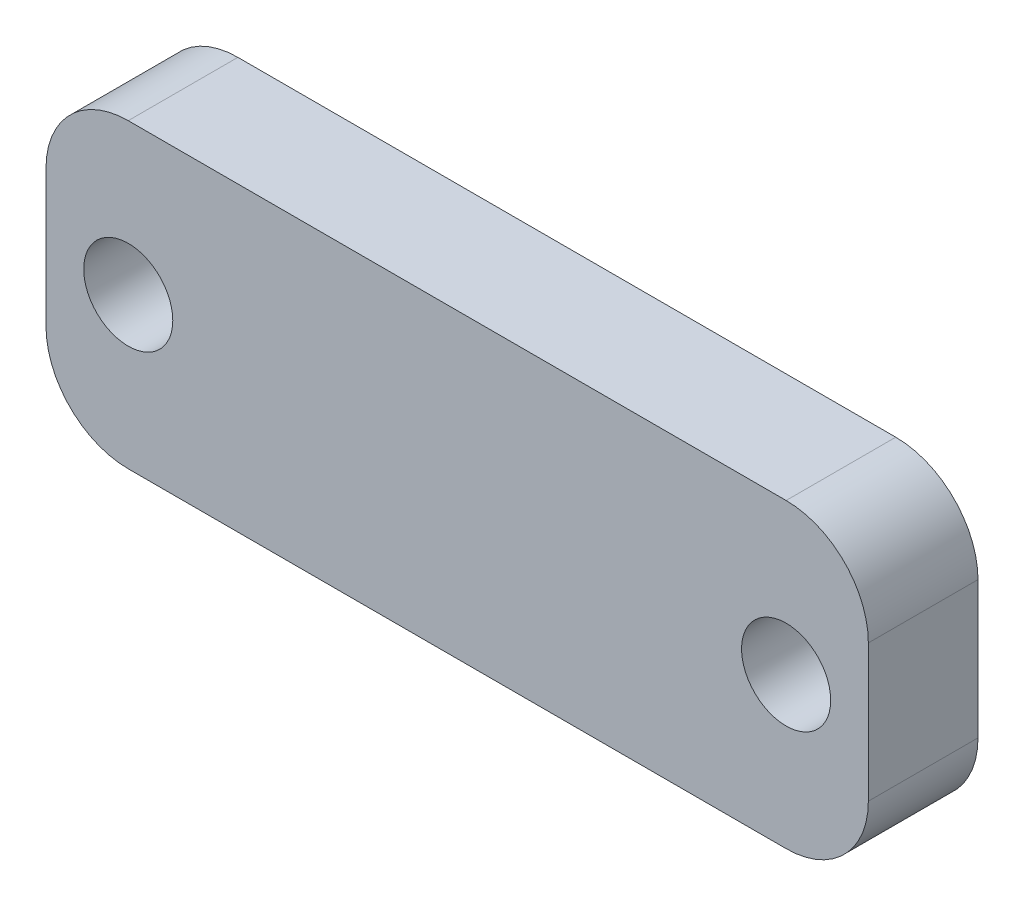
SolidWorks part; units mm, degrees
material "SS 304 (Default)"
ref_plane "Front Plane" through (0, 0, 0) normal (0, 0, 1) x (1, 0, 0)
ref_plane "Top Plane" through (0, 0, 0) normal (0, 1, 0) x (1, 0, 0)
ref_plane "Right Plane" through (0, 0, 0) normal (1, 0, 0) x (0, 0, -1)
sketch "Sketch1" plane through (0, 0, 0) normal (0, 0, 1) x (1, 0, 0)
  line L1 (47.625, 17.4625) -> (-47.625, 17.4625)
  line L2 (47.625, 17.4625) -> (47.625, -17.4625)
  line L3 (47.625, -17.4625) -> (-47.625, -17.4625)
  line L4 (-47.625, 17.4625) -> (-47.625, -17.4625)
  line L5 (47.625, 17.4625) -> (-47.625, -17.4625) construction
  line L6 (47.625, -17.4625) -> (-47.625, 17.4625) construction
  point P0 (0, 0)
  dimension "D1" = 95.25
  dimension "D2" = 34.925
sheet metal parameters "Sheet-Metal1" thickness 12.7 parameters "D1"=8.7312
base flange "Base-Flange1" sketch "Sketch1" thickness 12.7 reverse thickness direction yes parameters "D1"=8.7312
sketch "Sketch2" plane through (0, 0, 0) normal (0, 0, 1) x (1, 0, 0)
  circle A0 centre (0, 0) radius 12.827
  dimension "D1" = 25.654
extrude "Cut-Extrude1" cut sketch "Sketch2" along normal blind 4.7625 normal cut yes
hole_wizard "13/32 (0.40625) Diameter Hole1" positions "Sketch3" profile "Sketch4" hole size "13/32" standard "ANSI Inch" end condition up to next
sketch "Sketch3" plane through (0, 0, 12.7) normal (0, 0, 1) x (1, 0, 0)
  point P0 (38.1, 0)
  point P2 (-38.1, 0)
  dimension "D1" = 76.2
  dimension "D2" = 38.1
sketch "Sketch4" plane through (38.1, 0, 12.7) normal (1, 0, 0) x (0, -1, 0)
  line L0 (0, 0) -> (0, 12.7)
  line L1 (0, 12.7) -> (5.1594, 12.7)
  line L2 (5.1594, 12.7) -> (5.1594, 0)
  line L5 (5.1594, 0) -> (0, 0)
  line L11 (0, -6.35) -> (0, 107.95) construction
  dimension "Thru Hole Dia." = 10.3187
  dimension "Thru Hole Depth" = 12.7
chamfer "Chamfer1" distance 1.5875 angle 45 1 edges at (12.827, 0, 0)
fillet "Fillet1" radius 9.525 4 edges at (-47.625, -17.4625, 6.35) (-47.625, 17.4625, 6.35) (47.625, -17.4625, 6.35) (47.625, 17.4625, 6.35)
flat pattern "Flat-Pattern1" [suppressed]
sketch "Bend-Lines1" plane through (0, 0, 0) normal (0, 1, 0) x (-1, 0, 0)
sketch3d "Bounding-Box1" [suppressed]
  line L0 (0, 0.0001, 0) -> (95.25, 0.0001, 0) construction
  line L1 (0, 38.0999, 0) -> (95.25, 38.0999, 0) construction
  line L2 (0, 0.0001, 0) -> (0, 38.0999, 0) construction
  line L3 (95.25, 0.0001, 0) -> (95.25, 38.0999, 0) construction
